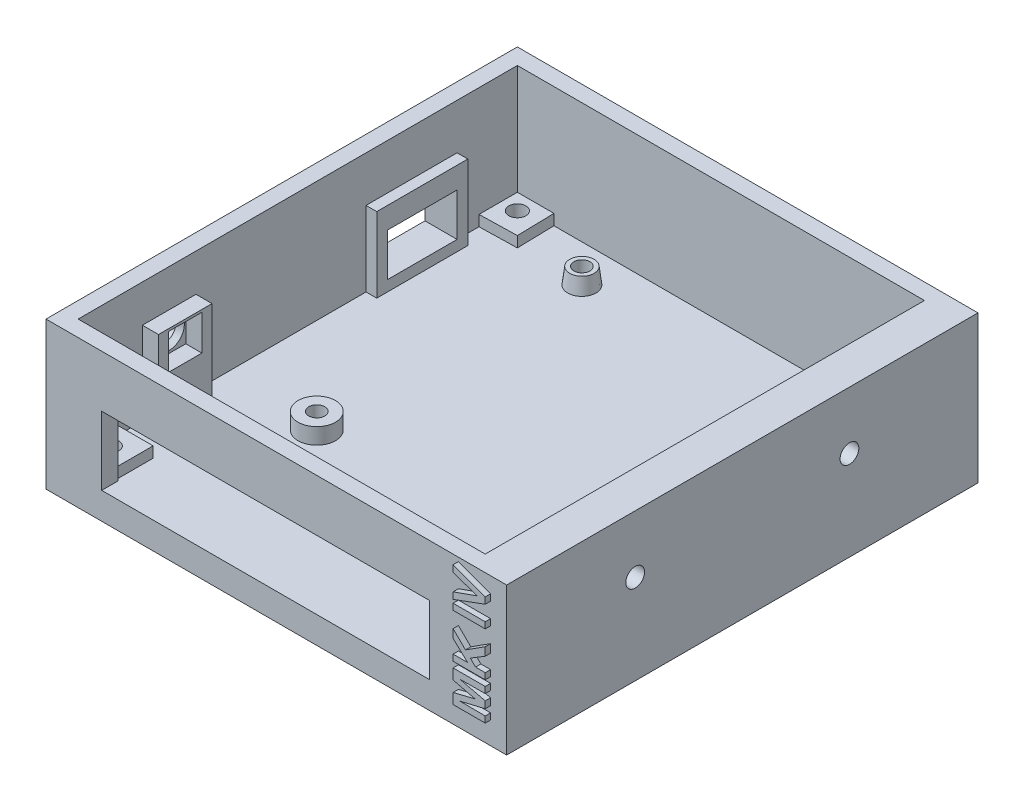
SolidWorks part; units mm, degrees
ref_plane "Спереди" through (0, 0, 0) normal (0, 0, 1) x (1, 0, 0)
ref_plane "Сверху" through (0, 0, 0) normal (0, 1, 0) x (1, 0, 0)
ref_plane "Справа" through (0, 0, 0) normal (1, 0, 0) x (0, 0, -1)
sketch "Sketch1" plane through (0, 0, 0) normal (0, 1, 0) x (1, 0, 0)
  line L1 (41, 44) -> (-41, 44)
  line L2 (41, 44) -> (41, -44)
  line L3 (41, -44) -> (-41, -44)
  line L4 (-41, 44) -> (-41, -44)
  line L5 (41, 44) -> (-41, -44) construction
  line L6 (41, -44) -> (-41, 44) construction
  point P0 (0, 0)
  dimension "D1" = 82
  dimension "D2" = 88
extrude "Boss-Extrude1" add sketch "Sketch1" along normal blind 5
sketch "Sketch2" plane through (0, 5, 0) normal (0, 1, 0) x (1, 0, 0)
  line L1 (-41, 44) -> (41, 44)
  line L2 (-41, 44) -> (-41, -44)
  line L3 (-41, -44) -> (41, -44)
  line L4 (41, 44) -> (41, -44)
  line L5 (-41, 44) -> (41, -44) construction
  line L6 (-41, -44) -> (41, 44) construction
  line L7 (-38, 41) -> (38, 41)
  line L8 (-38, 41) -> (-38, -41)
  line L9 (-38, -41) -> (38, -41)
  line L10 (38, 41) -> (38, -41)
  line L11 (-38, 41) -> (38, -41) construction
  line L12 (-38, -41) -> (38, 41) construction
  point P0 (0, 0)
  point P7 (0, 0)
  dimension "D1" = 3
  dimension "D2" = 3
  dimension "D3" = 76
  dimension "D4" = 82
  dimension "D5" = 82
  dimension "D6" = 88
extrude "Boss-Extrude2" add sketch "Sketch2" along normal blind 22.5
sketch "Эскиз1" plane through (0, 5, 0) normal (0, 1, 0) x (1, 0, 0)
  line L0 (-34.3, 36.65) -> (34.3, 36.65) construction
  line L1 (34.3, -16.65) -> (-34.3, 36.65) construction
  line L2 (-34.3, -16.65) -> (34.3, 36.65) construction
  line L3 (0, 41) -> (0, -41) construction
  line L4 (-38, -41) -> (38, -41) construction
  line L5 (31.8, -14.15) -> (-34.3, -14.15) construction
  line L6 (38, 41) -> (-38, 41) construction
  line L7 (34.3, 36.65) -> (34.3, -16.65) construction
  line L8 (34.3, -16.65) -> (-34.3, -16.65) construction
  line L9 (-34.3, -16.65) -> (-34.3, 36.65) construction
  line L10 (-34.3, 36.65) -> (-20.3, 36.65) construction
  line L11 (31.8, 36.65) -> (31.8, 18.85) construction
  line L12 (31.8, 18.85) -> (31.8, 34.05) construction
  line L13 (-20.3, 36.65) -> (-19, 36.65) construction
  line L14 (-20.3, 36.65) -> (-20.3, -16.65) construction
  line L15 (-19, 36.65) -> (31.8, 36.65) construction
  line L16 (31.8, 36.65) -> (31.8, -16.65) construction
  line L17 (31.8, -16.65) -> (31.8, -14.15) construction
  line L18 (31.8, 34.05) -> (-19, 34.05) construction
  line L19 (-19, 36.65) -> (-19, -16.65) construction
  circle A0 centre (31.8, -9.05) radius 1.5
  circle A1 centre (-20.3, -14.15) radius 1.5
  circle A2 centre (31.8, 18.85) radius 1.5
  circle A3 centre (-19, 34.05) radius 1.5
  circle A4 centre (-20.3, -14.15) radius 3.5
  circle A5 centre (-19, 34.05) radius 3.5
  circle A6 centre (31.8, 18.85) radius 3.5
  circle A7 centre (31.8, -9.05) radius 3.5
  point P3 (0, 10)
  point P11 (-20.3, -14.15)
  point P34 (0, 0)
  dimension "D12" = 3
  dimension "D2" = 7
  dimension "D3" = 53.3
  dimension "D4" = 68.6
  dimension "D5" = 14
  dimension "D6" = 1.3
  dimension "D7" = 50.8
  dimension "D8" = 2.5
  dimension "D9" = 5.1
  dimension "D10" = 27.9
  dimension "D11" = 15.2
  dimension "D13" = 31
extrude "Boss-Extrude3" add sketch "Эскиз1" along normal blind 3
sketch "Sketch4" plane through (-41, 0, 0) normal (-1, 0, 0) x (0, 0, 1)
  line L0 (0, 27.5) -> (0, 0) construction
  line L1 (-27.75, 17) -> (-14.75, 17)
  line L2 (-27.75, 27.5) -> (-27.75, 5) construction
  line L3 (-44, 0) -> (44, 0) construction
  line L4 (-14.75, 5) -> (-14.75, 27.5) construction
  line L5 (26.75, 5) -> (-26.75, 5) construction
  line L6 (-44, 27.5) -> (44, 27.5) construction
  line L7 (-27.75, 17) -> (-27.75, 5)
  line L8 (-27.75, 5) -> (-14.75, 5)
  line L9 (-41, 5) -> (41, 5) construction
  line L10 (-14.75, 5) -> (-14.75, 17)
  line L11 (-44, 27.5) -> (-44, 0) construction
  point P7 (0, 5)
  point P8 (-21.25, 5)
  dimension "D1" = 53.5
  dimension "D2" = 16.25
  dimension "D3" = 13
  dimension "D4" = 12
extrude "Cut-Extrude1" cut sketch "Sketch4" against normal up to surface (3 mm away) up to face at (-38, 16.25, 0)
sketch "Sketch7" plane through (0, 0, 0) normal (0, -1, 0) x (1, 0, 0)
  line L0 (-41, -44) -> (-41, 44) construction
  line L1 (-35, 38) -> (35, -38) construction
  line L2 (35, -38) -> (-35, -38) construction
  line L3 (-35, -38) -> (-35, 38) construction
  line L4 (-35, 38) -> (35, 38) construction
  line L5 (35, 38) -> (35, -38) construction
  line L6 (-41, 44) -> (41, 44) construction
  line L8 (41, 44) -> (41, -44) construction
  line L9 (41, -44) -> (-41, -44) construction
  circle A0 centre (35, -38) radius 1.6
  circle A1 centre (-35, -38) radius 1.6
  circle A2 centre (-35, 38) radius 1.6
  circle A3 centre (35, 38) radius 1.6
  dimension "D2" = 3.2
  dimension "D3" = 6
  dimension "D1" = 6
  dimension "D4" = 6
  dimension "D5" = 6
extrude "Cut-Extrude3" cut sketch "Sketch7" against normal through all
sketch "Sketch8" plane through (0, 0, 0) normal (0, -1, 0) x (1, 0, 0)
  line L0 (-41, 44) -> (41, 44) construction
  line L1 (33.375, 35.1854) -> (36.625, 35.1854)
  line L2 (36.625, 35.1854) -> (38.25, 38)
  line L3 (38.25, 38) -> (36.625, 40.8146)
  line L4 (36.625, 40.8146) -> (33.375, 40.8146)
  line L5 (33.375, 40.8146) -> (31.75, 38)
  line L6 (31.75, 38) -> (33.375, 35.1854)
  line L7 (33.375, -35.1854) -> (31.75, -38)
  line L8 (31.75, -38) -> (33.375, -40.8146)
  line L9 (33.375, -40.8146) -> (36.625, -40.8146)
  line L10 (36.625, -40.8146) -> (38.25, -38)
  line L11 (38.25, -38) -> (36.625, -35.1854)
  line L12 (36.625, -35.1854) -> (33.375, -35.1854)
  line L13 (-36.625, -35.1854) -> (-38.25, -38)
  line L14 (-38.25, -38) -> (-36.625, -40.8146)
  line L15 (-36.625, -40.8146) -> (-33.375, -40.8146)
  line L16 (-33.375, -40.8146) -> (-31.75, -38)
  line L17 (-31.75, -38) -> (-33.375, -35.1854)
  line L18 (-33.375, -35.1854) -> (-36.625, -35.1854)
  line L19 (-36.625, 35.1854) -> (-33.375, 35.1854)
  line L20 (-33.375, 35.1854) -> (-31.75, 38)
  line L21 (-31.75, 38) -> (-33.375, 40.8146)
  line L22 (-33.375, 40.8146) -> (-36.625, 40.8146)
  line L23 (-36.625, 40.8146) -> (-38.25, 38)
  line L24 (-38.25, 38) -> (-36.625, 35.1854)
  line L25 (41, -44) -> (-41, -44) construction
  circle A0 centre (35, 38) radius 3.25 construction
  circle A1 centre (35, -38) radius 3.25 construction
  circle A2 centre (-35, -38) radius 3.25 construction
  circle A3 centre (-35, 38) radius 3.25 construction
  dimension "D1" = 6.5
extrude "Cut-Extrude4" cut sketch "Sketch8" against normal blind 3.5
sketch "Sketch10" plane through (-38, 0, 0) normal (1, 0, 0) x (0, 0, -1)
  line L0 (27.75, 17) -> (14.75, 5) construction
  line L2 (14.75, 5) -> (27.75, 5)
  line L3 (14.75, 5) -> (14.75, 17)
  line L4 (14.75, 17) -> (27.75, 17)
  line L5 (27.75, 5) -> (27.75, 17)
  line L6 (14.75, 5) -> (27.75, 17) construction
  line L7 (14.75, 17) -> (27.75, 5) construction
  line L8 (12.75, 3) -> (29.75, 3)
  line L9 (12.75, 3) -> (12.75, 19)
  line L10 (12.75, 19) -> (29.75, 19)
  line L11 (29.75, 3) -> (29.75, 19)
  line L12 (12.75, 3) -> (29.75, 19) construction
  line L13 (12.75, 19) -> (29.75, 3) construction
  point P4 (21.25, 11)
  point P5 (21.25, 11)
  dimension "D1" = 2
  dimension "D2" = 2
extrude "Boss-Extrude6" add sketch "Sketch10" along normal blind 2
chamfer "Chamfer1" distance 10 angle 7 1 edges at (-19, 8, -30.55) first distance on face at (-19, 8, -30.55)
sketch "Sketch11" plane through (0, 5, 0) normal (0, 1, 0) x (1, 0, 0)
  circle A0 centre (-20.3, -14.15) radius 1.5
  circle A1 centre (-19, 34.05) radius 1.5
  circle A2 centre (31.8, -9.05) radius 1.5
  circle A3 centre (31.8, 18.85) radius 1.5
  circle A4 centre (31.8, 18.85) radius 1.5 construction
extrude "Cut-Extrude5" cut sketch "Sketch11" against normal through all
sketch "Sketch12" plane through (0, 0, 44) normal (0, 0, 1) x (1, 0, 0)
  line L0 (-41, 11.4) -> (41, 11.4) construction
  line L1 (-41, 27.5) -> (-41, 0) construction
  line L2 (41, 27.5) -> (41, 0) construction
  line L3 (-38, 5) -> (38, 5) construction
  line L4 (30.6, 17.8) -> (-30.6, 17.8)
  line L5 (30.6, 17.8) -> (30.6, 5)
  line L6 (30.6, 5) -> (-30.6, 5)
  line L7 (-30.6, 17.8) -> (-30.6, 5)
  line L8 (30.6, 17.8) -> (-30.6, 5) construction
  line L9 (30.6, 5) -> (-30.6, 17.8) construction
  point P6 (0, 11.4)
  dimension "D1" = 12.8
  dimension "D2" = 61.2
extrude "Cut-Extrude6" cut sketch "Sketch12" against normal up to surface (3 mm away) up to face at (0, 16.25, 41)
sketch "Sketch13" plane through (41, 0, 0) normal (1, 0, 0) x (0, 0, -1)
  line L0 (-44, 16.75) -> (44, 16.75) construction
  line L3 (-44, 27.5) -> (-44, 0) construction
  line L4 (44, 27.5) -> (44, 0) construction
  circle A0 centre (-20, 16.75) radius 1.75
  circle A1 centre (20, 16.75) radius 1.75
  point P10 (0, 16.75)
  point P11 (-44, 13.75)
  dimension "D1" = 40
  dimension "D4" = 3.5
  dimension "D2" = 20
  dimension "D3" = 3
extrude "Cut-Extrude7" cut sketch "Sketch13" against normal up to surface (3 mm away) up to face at (38, 16.25, 0)
sketch "Sketch14" plane through (41, 0, 0) normal (1, 0, 0) x (0, 0, -1)
  line L0 (-44, 13.75) -> (44, 13.75) construction
  line L1 (-44, 27.5) -> (-44, 0) construction
  line L2 (44, 27.5) -> (44, 0) construction
  line L4 (44, 0) -> (-44, 0)
  line L5 (44, 0) -> (44, 27.5)
  line L6 (44, 27.5) -> (-44, 27.5)
  line L7 (-44, 0) -> (-44, 27.5)
  line L8 (44, 0) -> (-44, 27.5) construction
  line L9 (44, 27.5) -> (-44, 0) construction
  circle A0 centre (-20, 16.75) radius 1.75
  circle A1 centre (20, 16.75) radius 1.75
  circle A2 centre (20, 16.75) radius 1.75 construction
  point P6 (0, 13.75)
extrude "Boss-Extrude7" add sketch "Sketch14" along normal blind 4
sketch "Sketch15" plane through (38, 0, 0) normal (-1, 0, 0) x (0, 0, 1)
  circle A0 centre (20, 16.75) radius 3.75
  circle A1 centre (-20, 16.75) radius 3.75
  dimension "D1" = 7.5
extrude "Cut-Extrude8" cut sketch "Sketch15" against normal blind 3
sketch "Sketch16" plane through (-41, 0, 0) normal (-1, 0, 0) x (0, 0, 1)
  line L0 (44, 16.75) -> (-44, 16.75) construction
  line L1 (44, 27.5) -> (44, 0) construction
  line L2 (-44, 27.5) -> (-44, 0) construction
  circle A0 centre (24, 16.75) radius 2.25
  point P6 (44, 13.75)
  dimension "D2" = 4.5
  dimension "D1" = 3
  dimension "D3" = 20
extrude "Cut-Extrude9" cut sketch "Sketch16" against normal up to next
sketch "Sketch17" plane through (-38, 0, 0) normal (1, 0, 0) x (0, 0, -1)
  line L0 (-29, 20.5) -> (-29, 5)
  line L1 (-20.9, 13.45) -> (-27.1, 13.45)
  line L2 (-20.9, 13.45) -> (-20.9, 20.05)
  line L3 (-20.9, 20.05) -> (-27.1, 20.05)
  line L4 (-27.1, 13.45) -> (-27.1, 20.05)
  line L5 (-20.9, 13.45) -> (-27.1, 20.05) construction
  line L6 (-20.9, 20.05) -> (-27.1, 13.45) construction
  line L7 (12.75, 5) -> (-41, 5) construction
  line L8 (-29, 5) -> (-19, 5)
  line L9 (-19, 20.5) -> (-29, 20.5)
  line L10 (-19, 5) -> (-19, 20.5)
  line L11 (-17.8, 12.1) -> (-29, 20.5) construction
  line L12 (-19, 20.5) -> (-29, 13) construction
  point P0 (-24, 16.75)
  point P6 (-24, 16.75)
  dimension "D1" = 6.2
  dimension "D3" = 10
extrude "Boss-Extrude8" add sketch "Sketch17" along normal blind 3
chamfer "Chamfer2" distance 1 angle 30 1 edges at (-38, 16.75, 21.75) first distance on face at (-38, 16.75, 21.75)
sketch "Sketch20" plane through (-41, 0, 0) normal (-1, 0, 0) x (0, 0, 1)
  circle A0 centre (24, 16.75) radius 3
  circle A1 centre (24, 16.75) radius 5
  dimension "D1" = 6
  dimension "D2" = 10
extrude "Boss-Extrude10" add sketch "Sketch20" along normal blind 1
fillet "Fillet3" radius 2 1 edges at (-41, 16.75, 19)
sketch "Sketch21" plane through (0, 5, 0) normal (0, 1, 0) x (1, 0, 0)
  line L0 (-41, 27.75) -> (-36, 27.75)
  line L1 (-36, 27.75) -> (-36, 14.75)
  line L2 (-36, 14.75) -> (-41, 14.75)
  line L3 (-41, 14.75) -> (-41, 27.75)
extrude "Boss-Extrude11" add sketch "Sketch21" along normal blind 2
sketch "Sketch22" plane through (0, 0, 44) normal (0, 0, 1) x (1, 0, 0)
  line L0 (42, 0) -> (42, 27.5) construction
  line L1 (-41, 0) -> (45, 0) construction
  line L2 (-41, 27.5) -> (45, 27.5) construction
  line L3 (45, 27.5) -> (45, 0) construction
  text T0 "<b> MK IV</b>" font "Arial" height 6
  dimension "D1" = 3
extrude "Boss-Extrude12" add sketch "Sketch22" along normal blind 1
sketch "Sketch27" plane through (0, 17, 0) normal (0, -1, 0) x (1, 0, 0)
  line L0 (-41, -27.75) -> (-41, -14.75)
  line L1 (-41, -14.75) -> (-36, -14.75)
  line L2 (-36, -14.75) -> (-36, -27.75)
  line L3 (-36, -27.75) -> (-41, -27.75)
extrude "Boss-Extrude17" add sketch "Sketch27" along normal blind 2
sketch "Sketch23" plane through (0, 5, 0) normal (0, 1, 0) x (1, 0, 0)
  line L2 (-31, -41) -> (-31, -34)
  line L3 (-38, -41) -> (-30.6, -41) construction
  line L4 (-38, -29) -> (-38, -41) construction
  line L5 (-38, -34) -> (-38, -41)
  line L6 (-31, -34) -> (-38, -34)
  line L7 (-31, -41) -> (-38, -41)
  line L8 (31, -41) -> (31, -34)
  line L9 (30.6, -41) -> (38, -41) construction
  line L10 (31, -34) -> (38, -34)
  line L11 (38, -41) -> (38, 41) construction
  line L12 (38, -34) -> (38, -41)
  line L13 (38, -41) -> (31, -41)
  line L14 (38, 34) -> (31, 34)
  line L15 (31, 34) -> (31, 41)
  line L16 (38, 41) -> (-38, 41) construction
  line L17 (31, 41) -> (38, 41)
  line L18 (38, 41) -> (38, 34)
  line L19 (-38, 41) -> (-38, 29.75) construction
  line L20 (-38, 33.8379) -> (-31.0019, 34.0019)
  line L21 (-31.0019, 34.0019) -> (-31.1659, 41)
  line L22 (-31.1659, 41) -> (-38, 41)
  line L23 (-38, 41) -> (-38, 33.8379)
  circle A4 centre (-35, -38) radius 1.6
  circle A5 centre (-35, 38) radius 1.6
  circle A6 centre (35, 38) radius 1.6
  circle A7 centre (35, -38) radius 1.6
  circle A8 centre (-35, -38) radius 1.6 construction
  dimension "D1" = 7
extrude "Boss-Extrude13" add sketch "Sketch23" along normal blind 2
sketch "Sketch25" plane through (-41, 0, 0) normal (-1, 0, 0) x (0, 0, 1)
  line L0 (-27.75, 11) -> (-14.75, 11) construction
  line L1 (-27.75, 15) -> (-27.75, 7) construction
  line L2 (-14.75, 7) -> (-14.75, 15) construction
  line L4 (-14.75, 7) -> (-27.75, 7)
  line L5 (-14.75, 7) -> (-14.75, 15)
  line L6 (-14.75, 15) -> (-27.75, 15)
  line L7 (-27.75, 7) -> (-27.75, 15)
  line L8 (-14.75, 7) -> (-27.75, 15) construction
  line L9 (-14.75, 15) -> (-27.75, 7) construction
  line L10 (-12.75, 5) -> (-29.75, 5)
  line L11 (-12.75, 5) -> (-12.75, 17)
  line L12 (-12.75, 17) -> (-29.75, 17)
  line L13 (-29.75, 5) -> (-29.75, 17)
  line L14 (-12.75, 5) -> (-29.75, 17) construction
  line L15 (-12.75, 17) -> (-29.75, 5) construction
  point P6 (-21.25, 11)
  point P12 (-21.25, 11)
  dimension "D1" = 2
  dimension "D2" = 2
extrude "Boss-Extrude15" add sketch "Sketch25" along normal up to surface (1 mm away) up to face at (-42, 16.75, 29)
fillet "Fillet4" radius 2 4 edges at (-41, 17, -21.25) (-41, 11, -29.75) (-41, 5, -21.25) (-41, 11, -12.75)
